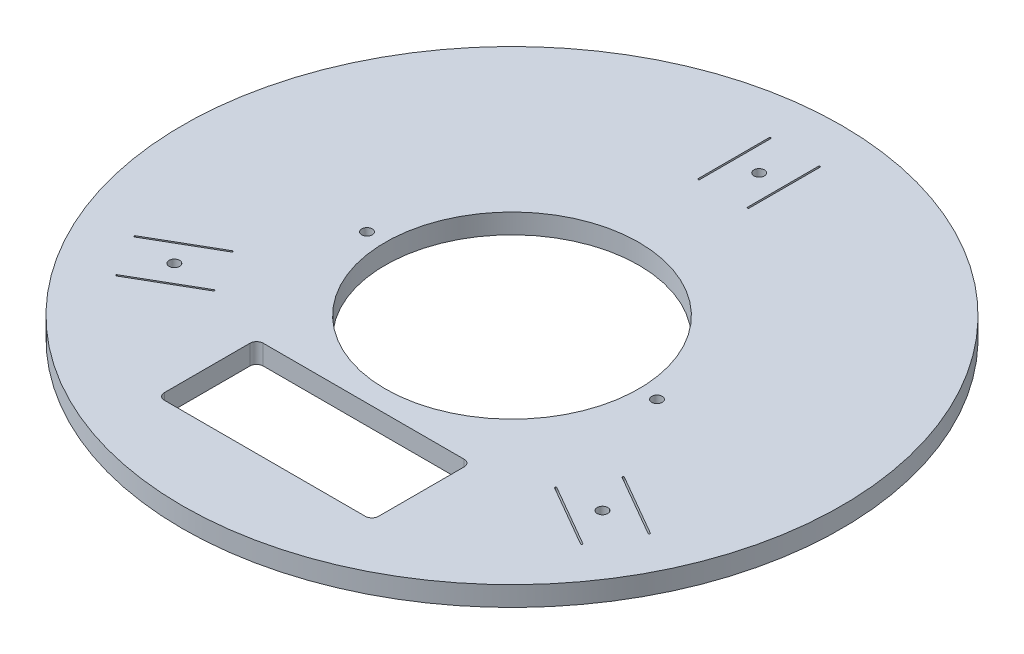
SolidWorks part; units mm, degrees
ref_plane "Front Plane" through (0, 0, 0) normal (0, 0, 1) x (1, 0, 0)
ref_plane "Top Plane" through (0, 0, 0) normal (0, 1, 0) x (1, 0, 0)
ref_plane "Right Plane" through (0, 0, 0) normal (1, 0, 0) x (0, 0, -1)
sketch "Sketch2" plane through (0, 0, 0) normal (0, 1, 0) x (1, 0, 0)
  circle A0 centre (0, 0) radius 100
  dimension "D1" = 200
extrude "Boss-Extrude1" add sketch "Sketch2" along normal blind 6
sketch "Sketch3" plane through (0, 6, 0) normal (0, 1, 0) x (1, 0, 0)
  line L0 (0, 0) -> (0, 100) construction
  line L1 (-7.5, 75) -> (7.5, 75) construction
  line L3 (-7.75, 64) -> (-7.25, 64)
  line L4 (-7.75, 64) -> (-7.75, 86)
  line L5 (-7.75, 86) -> (-7.25, 86)
  line L6 (-7.25, 64) -> (-7.25, 86)
  line L7 (-7.75, 64) -> (-7.25, 86) construction
  line L8 (-7.75, 86) -> (-7.25, 64) construction
  line L9 (7.25, 64) -> (7.75, 64)
  line L10 (7.25, 64) -> (7.25, 86)
  line L11 (7.25, 86) -> (7.75, 86)
  line L12 (7.75, 64) -> (7.75, 86)
  line L13 (7.25, 64) -> (7.75, 86) construction
  line L14 (7.25, 86) -> (7.75, 64) construction
  line L30 (59.3006, -25.2883) -> (78.3532, -36.2883)
  line L31 (59.3006, -25.2883) -> (59.0506, -25.7213)
  line L32 (59.0506, -25.7213) -> (78.1032, -36.7213)
  line L33 (78.3532, -36.2883) -> (78.1032, -36.7213)
  line L34 (51.8006, -38.2787) -> (70.8532, -49.2787)
  line L35 (51.8006, -38.2787) -> (51.5506, -38.7117)
  line L36 (51.5506, -38.7117) -> (70.6032, -49.7117)
  line L37 (70.8532, -49.2787) -> (70.6032, -49.7117)
  line L38 (-51.5506, -38.7117) -> (-70.6032, -49.7117)
  line L39 (-51.5506, -38.7117) -> (-51.8006, -38.2787)
  line L40 (-51.8006, -38.2787) -> (-70.8532, -49.2787)
  line L41 (-70.6032, -49.7117) -> (-70.8532, -49.2787)
  line L42 (-59.0506, -25.7213) -> (-78.1032, -36.7213)
  line L43 (-59.0506, -25.7213) -> (-59.3006, -25.2883)
  line L44 (-59.3006, -25.2883) -> (-78.3532, -36.2883)
  line L45 (-78.1032, -36.7213) -> (-78.3532, -36.2883)
  circle A0 centre (0, 0) radius 100 construction
  circle A1 centre (0, 75) radius 1.6
  circle A2 centre (64.9519, -37.5) radius 1.6
  circle A3 centre (-64.9519, -37.5) radius 1.6
  point P8 (0, 75)
  point P36 (0, 0)
  point P37 (0, 0)
  point P44 (0, 0)
  dimension "D6" = 3.2
  dimension "D1" = 15
  dimension "D2" = 22
  dimension "D3" = 0.5
  dimension "D4" = 75
  dimension "D5" = 3
  dimension "D7" = 3
extrude "Cut-Extrude1" cut sketch "Sketch3" against normal through all
sketch "Sketch4" plane through (0, 6, 0) normal (0, 1, 0) x (1, 0, 0)
  circle A0 centre (0, 0) radius 38.5
  dimension "D1" = 77
extrude "Cut-Extrude2" cut sketch "Sketch4" against normal through all
sketch "Sketch5" plane through (0, 6, 0) normal (0, 1, 0) x (1, 0, 0)
  line L0 (0, 0) -> (50000, 0) construction
  line L1 (0, 0) -> (0, 50000) construction
  circle A0 centre (-44, 0) radius 1.6
  circle A1 centre (44, 0) radius 1.6
  dimension "D2" = 3.2
  dimension "D1" = 44
extrude "Cut-Extrude3" cut sketch "Sketch5" against normal through all
sketch "Sketch6" plane through (0, 6, 0) normal (0, 1, 0) x (1, 0, 0)
  line L1 (-32.5, -45) -> (32.5, -45)
  line L2 (-32.5, -45) -> (-32.5, -75)
  line L3 (-32.5, -75) -> (32.5, -75)
  line L4 (32.5, -45) -> (32.5, -75)
  point P4 (0, -45)
  dimension "D1" = 45
  dimension "D2" = 30
  dimension "D3" = 65
extrude "Cut-Extrude4" cut sketch "Sketch6" against normal through all
fillet "Fillet1" radius 2 4 edges at (32.5, 3, 45) (32.5, 3, 75) (-32.5, 3, 75) (-32.5, 3, 45)
fillet "Fillet2" radius 0.2 24 edges at (-7.75, 3, -64) (-7.75, 3, -86) (-7.25, 3, -86) (-7.25, 3, -64) (-51.5506, 3, 38.7117) (-70.6032, 3, 49.7117) (-70.8532, 3, 49.2787) (-59.3006, 3, 25.2883) (-59.0506, 3, 25.7213) (-78.1032, 3, 36.7213) (-78.3532, 3, 36.2883) (51.5506, 3, 38.7117) (51.8006, 3, 38.2787) (70.8532, 3, 49.2787) (70.6032, 3, 49.7117) (59.0506, 3, 25.7213) (59.3006, 3, 25.2883) (78.3532, 3, 36.2883) (78.1032, 3, 36.7213) (7.25, 3, -64) (7.25, 3, -86) (7.75, 3, -86) (7.75, 3, -64) (-51.8006, 3, 38.2787)
equation "\"Leg_Spacing\"=15"
equation "\"D1@Sketch3\"=\"Leg_Spacing\""
equation "\"Leaf_Spring_Slot_Width\"=22"
equation "\"D2@Sketch3\"=\"Leaf_Spring_Slot_Width\""
equation "\"Leaf_Spring_Thickness\"=0.5"
equation "\"D3@Sketch3\"=\"Leaf_Spring_Thickness\""
equation "\"Inner_Radius\"=75"
equation "\"D4@Sketch3\"=\"Inner_Radius\""
equation "\"Camera\"=77"
equation "\"D1@Sketch4\"=\"Camera\""
